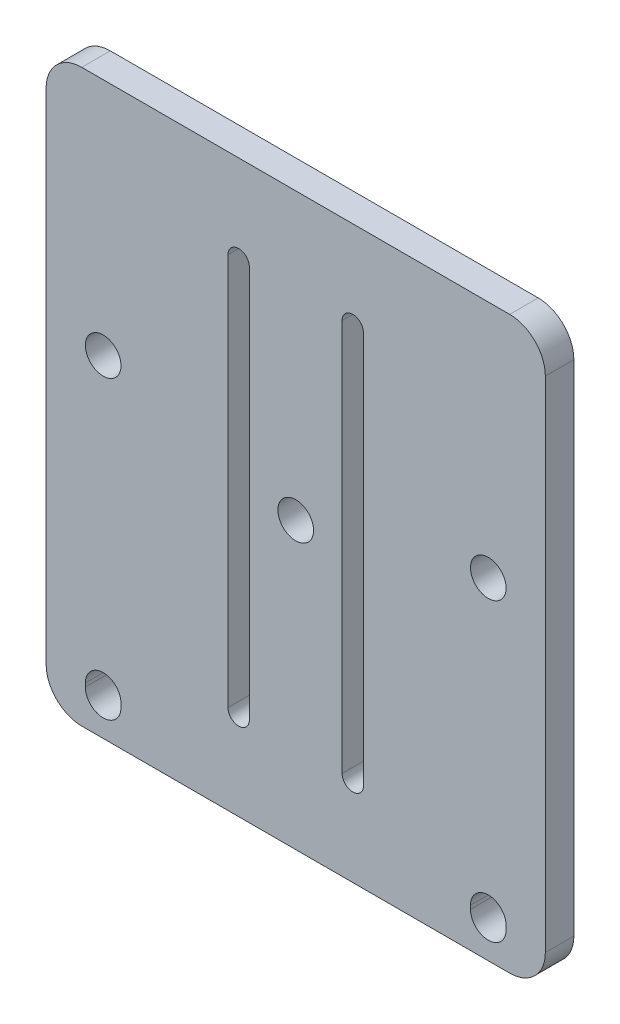
SolidWorks part; units mm, degrees
ref_plane "Front" through (0, 0, 0) normal (0, 0, 1) x (1, 0, 0)
ref_plane "Top" through (0, 0, 0) normal (0, 1, 0) x (1, 0, 0)
ref_plane "Right" through (0, 0, 0) normal (1, 0, 0) x (0, 0, -1)
sketch "Sketch4" plane through (0, 0, 0) normal (0, 0, 1) x (1, 0, 0)
  line L0 (-27, -34.5) -> (-27, -35) construction
  line L1 (-35, 40) -> (35, 40)
  line L2 (-35, 40) -> (-35, -40)
  line L3 (-35, -40) -> (35, -40)
  line L4 (35, 40) -> (35, -40)
  line L5 (-35, 40) -> (35, -40) construction
  line L6 (-35, -40) -> (35, 40) construction
  line L7 (-24.5, -34.5) -> (-24.5, -35)
  line L8 (-29.5, -34.5) -> (-29.5, -35)
  line L9 (0, -47.1607) -> (0, 39.6245) construction
  line L10 (27, -34.5) -> (27, -35) construction
  line L11 (24.5, -34.5) -> (24.5, -35)
  line L12 (29.5, -34.5) -> (29.5, -35)
  line L13 (-21.7344, 0) -> (13.0886, 0) construction
  line L14 (-15, 35) -> (15, 35) construction
  line L15 (-15, 35) -> (-15, -35) construction
  line L16 (-15, -35) -> (15, -35) construction
  line L17 (15, 35) -> (15, -35) construction
  line L18 (-15, 35) -> (15, -35) construction
  line L19 (-15, -35) -> (15, 35) construction
  circle A0 centre (-27, 6.5) radius 2.5
  arc A1 (-24.5, -34.5) -> (-29.5, -34.5) centre (-27, -34.5) ccw
  arc A2 (-29.5, -35) -> (-24.5, -35) centre (-27, -35) ccw
  arc A3 (24.5, -34.5) -> (29.5, -34.5) centre (27, -34.5) cw
  arc A4 (29.5, -35) -> (24.5, -35) centre (27, -35) cw
  circle A5 centre (27, 6.5) radius 2.5
  circle A6 centre (-15, 35) radius 1.5 construction
  circle A7 centre (15, 35) radius 1.5 construction
  circle A8 centre (15, -35) radius 1.5 construction
  circle A9 centre (-15, -35) radius 1.5 construction
  point P0 (0, 0)
  point P10 (-27, -34.75)
  point P19 (27, -34.75)
  point P28 (0, 0)
  dimension "D3" = 27
  dimension "D6" = 2.5
  dimension "D8" = 3
  dimension "D1" = 70
  dimension "D2" = 80
  dimension "D4" = 41
  dimension "D5" = 0.5
  dimension "D7" = 5
  dimension "D9" = 30
  dimension "D10" = 70
extrude "Boss-Extrude2" add sketch "Sketch4" along normal blind 4
fillet "Fillet1" radius 5 4 edges at (-35, -40, 2) (35, -40, 2) (35, 40, 2) (-35, 40, 2)
sketch "Sketch6" plane through (0, 0, 4) normal (0, 0, 1) x (1, 0, 0)
  line L0 (-8, 27.5) -> (-8, -27.5) construction
  line L3 (-6.5, 27.5) -> (-6.5, -27.5)
  line L4 (-9.5, 27.5) -> (-9.5, -27.5)
  line L8 (0, 19.4895) -> (0, -17.3057) construction
  line L11 (8, 27.5) -> (8, -27.5) construction
  line L15 (6.5, 27.5) -> (6.5, -27.5)
  line L18 (9.5, 27.5) -> (9.5, -27.5)
  arc A21 (-6.5, 27.5) -> (-9.5, 27.5) centre (-8, 27.5) ccw
  arc A22 (-9.5, -27.5) -> (-6.5, -27.5) centre (-8, -27.5) ccw
  arc A23 (6.5, 27.5) -> (9.5, 27.5) centre (8, 27.5) cw
  arc A24 (9.5, -27.5) -> (6.5, -27.5) centre (8, -27.5) cw
  circle A25 centre (0, 0) radius 2.5
  point P2 (-8, 0)
  point P11 (8, 0)
  dimension "D2" = 1.5
  dimension "D1" = 55
  dimension "D3" = 8
extrude "Cut-Extrude1" cut sketch "Sketch6" against normal through all
